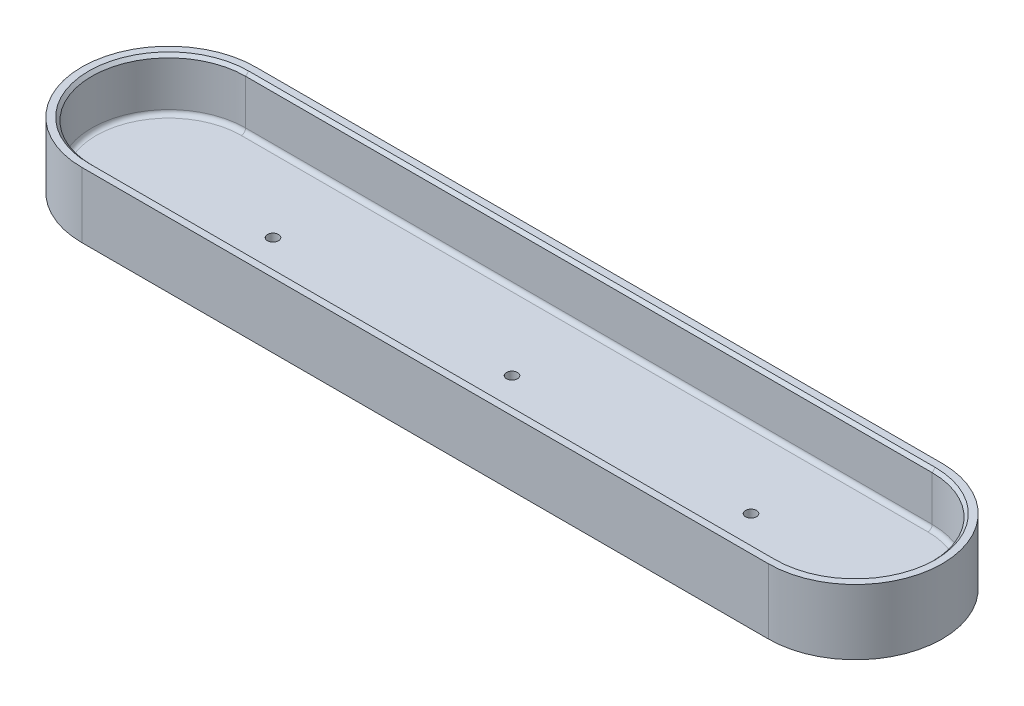
SolidWorks part; units mm, degrees
material "PLA"
ref_plane "Front Plane" through (0, 0, 0) normal (0, 0, 1) x (1, 0, 0)
ref_plane "Top Plane" through (0, 0, 0) normal (0, 1, 0) x (1, 0, 0)
ref_plane "Right Plane" through (0, 0, 0) normal (1, 0, 0) x (0, 0, -1)
sketch "Sketch1" plane through (0, 0, 0) normal (0, 1, 0) x (1, 0, 0)
  line L0 (-100.33, 0) -> (100.33, 0) construction
  line L1 (0, -55.9739) -> (0, 55.9739) construction
  line L2 (-100.33, 22.479) -> (100.33, 22.479)
  line L3 (-100.33, -22.479) -> (100.33, -22.479)
  arc A0 (-100.33, 22.479) -> (-100.33, -22.479) centre (-100.33, 0) ccw
  arc A1 (100.33, 22.479) -> (100.33, -22.479) centre (100.33, 0) cw
  circle A2 centre (-100.33, 0) radius 22.225 construction
  point P4 (0, 0)
  point P10 (0, 0)
  dimension "D2" = 0.254
  dimension "D3" = 44.45
  dimension "D1" = 200.66
extrude "MainBlock" add sketch "Sketch1" along normal blind 3.81
sketch "Sketch2" plane through (0, 0, 0) normal (0, -1, 0) x (1, 0, 0)
  line L0 (0, 0) -> (0, 50000) construction
  line L1 (-100.33, 25.4) -> (100.33, 25.4)
  line L2 (-100.33, -22.479) -> (100.33, -22.479)
  line L3 (100.33, 22.479) -> (-100.33, 22.479)
  line L5 (100.33, 22.479) -> (-100.33, 22.479)
  line L6 (-95.25, 0) -> (49904.75, 0) construction
  line L7 (100.33, -22.479) -> (-100.33, -22.479)
  line L8 (-100.33, -25.4) -> (100.33, -25.4)
  arc A0 (-100.33, 25.4) -> (-100.33, -25.4) centre (-100.33, 0) ccw
  arc A1 (100.33, 22.479) -> (100.33, -22.479) centre (100.33, 0) cw
  arc A2 (-100.33, 22.479) -> (-100.33, -22.479) centre (-100.33, 0) ccw
  arc A3 (100.33, -22.479) -> (100.33, 22.479) centre (100.33, 0) ccw
  arc A4 (-100.33, 22.479) -> (-100.33, -22.479) centre (-100.33, 0) ccw
  arc A6 (100.33, 25.4) -> (100.33, -25.4) centre (100.33, 0) cw
  point P0 (0, 22.479)
  point P15 (0, 25.4)
  point P16 (0, -22.479)
  point P19 (0, -25.4)
  dimension "2.1" = 50.8
  dimension "D1" = 0
extrude "Boss-Extrude1" add sketch "Sketch2" against normal blind 19.05
sketch "Sketch3" plane through (0, 0, 0) normal (0, -1, 0) x (1, 0, 0)
  line L0 (0, 0) -> (50000, 0) construction
  line L1 (0, 0) -> (0, 50000) construction
  circle A1 centre (0, 0) radius 1.6129
  circle A8 centre (-69.85, 0) radius 1.6129
  circle A9 centre (69.85, 0) radius 1.6129
  arc A10 (100.33, -25.4) -> (100.33, 25.4) centre (100.33, 0) ccw construction
  arc A11 (-100.33, 25.4) -> (-100.33, -25.4) centre (-100.33, 0) ccw construction
  arc A12 (100.33, -25.4) -> (100.33, 25.4) centre (100.33, 0) ccw construction
  arc A13 (-100.33, 25.4) -> (-100.33, -25.4) centre (-100.33, 0) ccw construction
  dimension "0.085" = 3.2258
  dimension "D2" = 3.2258
  dimension "D3" = 3.2258
  dimension "D4" = 30.48
  dimension "D5" = 30.48
extrude "Cut-Extrude1" cut sketch "Sketch3" against normal through all
fillet "Fillet1" radius 1.27 4 edges at (122.809, 3.81, 0) (0, 3.81, 22.479) (-122.809, 3.81, 0) (0, 3.81, -22.479)
chamfer "Chamfer1" distance 0.889 angle 45 4 edges at (0, 19.05, 22.479) (-122.809, 19.05, 0) (122.809, 19.05, 0) (0, 19.05, -22.479)
equation "\"D2@Sketch3\"=\"0.085@Sketch3\""
equation "\"D3@Sketch3\"=\"0.085@Sketch3\""
